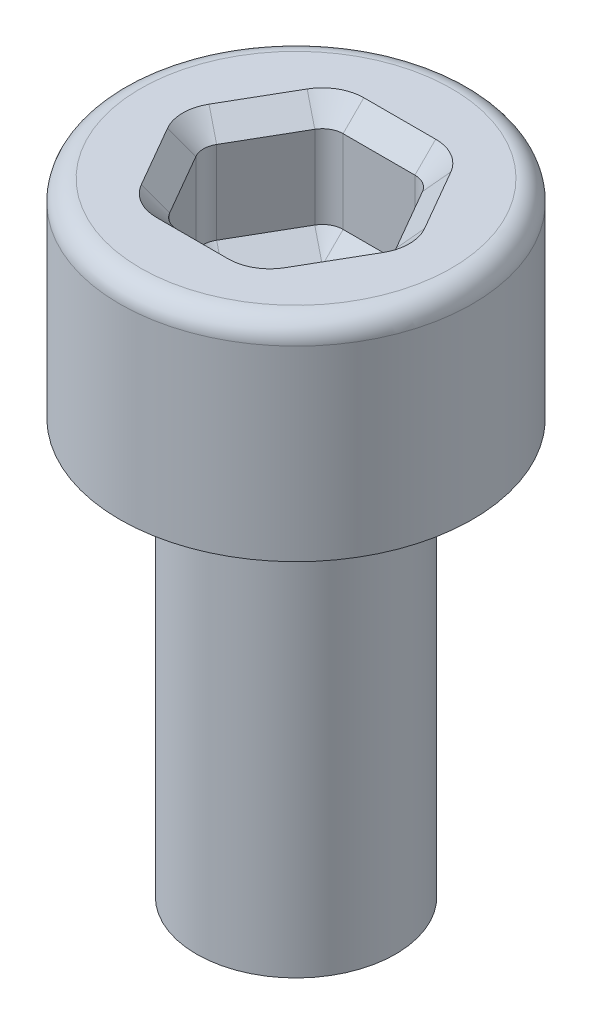
SolidWorks part; units mm, degrees
ref_plane "Front Plane" through (0, 0, 0) normal (0, 0, 1) x (1, 0, 0)
ref_plane "Top Plane" through (0, 0, 0) normal (0, 1, 0) x (1, 0, 0)
ref_plane "Right Plane" through (0, 0, 0) normal (1, 0, 0) x (0, 0, -1)
sketch "Sketch1" plane through (0, 0, 0) normal (0, 1, 0) x (1, 0, 0)
  circle A0 centre (0, 0) radius 2.4
  dimension "D1" = 4.8
extrude "Boss-Extrude1" add sketch "Sketch1" along normal blind 10
sketch "Sketch2" plane through (0, 10, 0) normal (0, 1, 0) x (1, 0, 0)
  circle A0 centre (0, 0) radius 4.25
  dimension "D1" = 8.5
extrude "Boss-Extrude2" add sketch "Sketch2" along normal blind 5
sketch "Sketch3" plane through (0, 15, 0) normal (0, 1, 0) x (1, 0, 0)
  line L1 (2.1651, 0.25) -> (1.299, 1.75)
  line L2 (0.866, 2) -> (-0.866, 2)
  line L3 (-1.299, 1.75) -> (-2.1651, 0.25)
  line L4 (-2.1651, -0.25) -> (-1.299, -1.75)
  line L5 (-0.866, -2) -> (0.866, -2)
  line L6 (1.299, -1.75) -> (2.1651, -0.25)
  circle A0 centre (0, 0) radius 2 construction
  arc A1 (-2.1651, 0.25) -> (-2.1651, -0.25) centre (-1.7321, 0) ccw
  arc A2 (-1.299, -1.75) -> (-0.866, -2) centre (-0.866, -1.5) ccw
  arc A3 (0.866, -2) -> (1.299, -1.75) centre (0.866, -1.5) ccw
  arc A4 (2.1651, -0.25) -> (2.1651, 0.25) centre (1.7321, 0) ccw
  arc A5 (1.299, 1.75) -> (0.866, 2) centre (0.866, 1.5) ccw
  arc A6 (-1.299, 1.75) -> (-0.866, 2) centre (-0.866, 1.5) cw
  point P1 (0, 0)
  point P10 (0, 0)
  point P11 (0, 2.3094)
  point P12 (0, 0)
  point P13 (-2.3094, 0)
  point P14 (0, 0)
  point P17 (-2.3094, 0)
  dimension "D2" = 0.5
  dimension "D1" = 4
extrude "Cut-Extrude1" cut sketch "Sketch3" against normal blind 3
chamfer "Chamfer1" distance 0.5 angle 45 24 edges at (1.7321, 15, 1) (2.2321, 15, 0) (1.116, 15, 1.933) (1.7321, 15, -1) (0, 15, 2) (1.116, 15, -1.933) (-1.116, 15, 1.933) (0, 15, -2) (-1.7321, 15, 1) (-1.116, 15, -1.933) (-2.2321, 15, 0) (-1.7321, 15, -1) (1.7321, 12, 1) (2.2321, 12, 0) (1.116, 12, 1.933) (1.7321, 12, -1) (0, 12, 2) (1.116, 12, -1.933) (-1.116, 12, 1.933) (0, 12, -2) (-1.7321, 12, 1) (-1.116, 12, -1.933) (-2.2321, 12, 0) (-1.7321, 12, -1)
fillet "Fillet1" radius 0.5 1 edges at (0, 15, 4.25)
